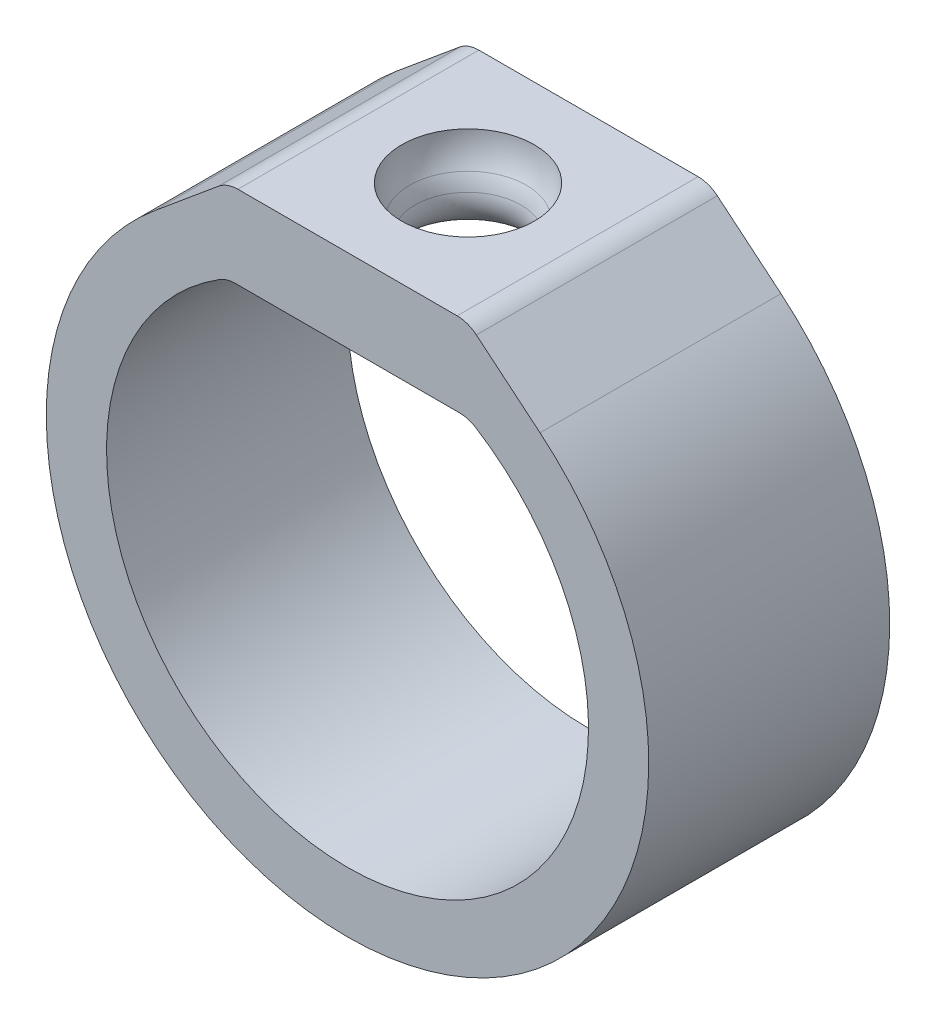
SolidWorks part; units mm, degrees
ref_plane "Front Plane" through (0, 0, 0) normal (0, 0, 1) x (1, 0, 0)
ref_plane "Top Plane" through (0, 0, 0) normal (0, 1, 0) x (1, 0, 0)
ref_plane "Right Plane" through (0, 0, 0) normal (1, 0, 0) x (0, 0, -1)
ref_axis "X Axis" through (-88.99, 0, 0) along (1, 0, 0)
ref_axis "Y Axis" through (0, 55, 0) along (0, -1, 0)
ref_axis "Z Axis" through (0, 0, -88.99) along (0, 0, 1)
sketch "Sketch1" plane through (0, 0, 0) normal (0, 0, 1) x (1, 0, 0)
  line L0 (0, 0) -> (0, 9.6782) construction
  line L1 (-4, 9.6782) -> (4, 9.6782)
  line L4 (-4, 6.9282) -> (4, 6.9282)
  line L5 (6.3913, 7.691) -> (4, 9.6782)
  line L6 (-6.3913, 7.691) -> (-4, 9.6782)
  circle A5 centre (0, 9.6782) radius 2 construction
  arc A6 (-4, 6.9282) -> (4, 6.9282) centre (0, 0) ccw
  arc A8 (6.3913, 7.691) -> (-6.3913, 7.691) centre (0, 0) cw
  point P0 (5.8539, 8.1075)
  point P3 (0, 0)
  point P7 (6.3913, 7.4491)
  point P9 (0, 0)
  dimension "D1" = 8
  dimension "D3" = 4
  dimension "D2" = 2
  dimension "D4" = 0.75
  dimension "D5" = 8
extrude "Boss-Extrude1" add sketch "Sketch1" along normal mid plane 8
sketch "Sketch2" plane through (0, 0, 0) normal (0, 0, 1) x (1, 0, 0)
  line L0 (0, 0) -> (0, 9.6782) construction
  line L1 (0, 0) -> (0, 11.8782) construction
  line L2 (1.5, 7.6782) -> (1.5, 6.9282) construction
  line L3 (-4, 6.9282) -> (4, 6.9282) construction
  line L4 (1.5, 6.9282) -> (0, 6.9282) construction
  line L5 (1.5, 7.6782) -> (0, 7.6782) construction
  line L6 (0, 6.7282) -> (0, 11.8782)
  line L7 (1.7, 6.7282) -> (0, 6.7282)
  line L8 (1.7, 7.6782) -> (1.7, 6.7282)
  circle A0 centre (0, 9.6782) radius 2 construction
  arc A1 (1.7647, 8.737) -> (0, 11.6782) centre (0, 9.6782) ccw construction
  arc A2 (1.7647, 8.737) -> (1.5, 7.6782) centre (3.75, 7.6782) ccw construction
  arc A3 (1.9412, 8.6429) -> (1.7, 7.6782) centre (3.75, 7.6782) ccw
  arc A4 (1.9412, 8.6429) -> (0, 11.8782) centre (0, 9.6782) ccw
  dimension "D1" = 1.5
  dimension "D2" = 0.2
revolve "Cut-Revolve1" cut sketch "Sketch2" angle 360 about L6
fillet "Fillet2" radius 1 1 edges at (0, 6.9282, -1.7)
fillet "Fillet3" radius 1 4 edges at (-4, 9.6782, 0) (4, 9.6782, 0) (4, 6.9282, 0) (-4, 6.9282, 0)
